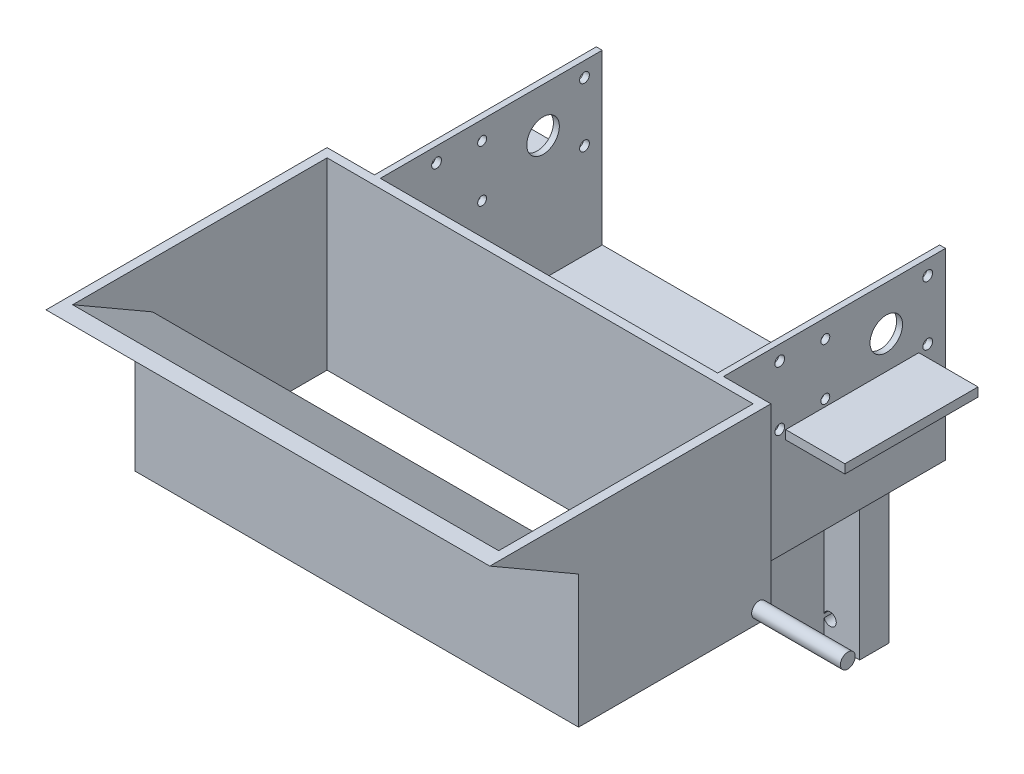
SolidWorks part; units mm, degrees
other "标注1"
sketch "草图12" plane through (40, 25, 80) normal (0.0849, 0.2202, 0.9717) x (0.9962, -0.0022, -0.0865)
ref_plane "前视基准面" through (0, 0, 0) normal (0, 0, 1) x (1, 0, 0)
ref_plane "上视基准面" through (0, 0, 0) normal (0, 1, 0) x (1, 0, 0)
ref_plane "右视基准面" through (0, 0, 0) normal (1, 0, 0) x (0, 0, -1)
sketch "草图1" plane through (0, 0, 0) normal (0, 0, 1) x (1, 0, 0)
  line L1 (-40, -25) -> (40, -25)
  line L2 (-40, -25) -> (-40, 25)
  line L3 (-40, 25) -> (40, 25)
  line L4 (40, -25) -> (40, 25)
  line L5 (-40, -25) -> (40, 25) construction
  line L6 (-40, 25) -> (40, -25) construction
  point P0 (0, 0)
  dimension "D1" = 80
  dimension "D2" = 50
extrude "凸台-拉伸1" add sketch "草图1" along normal blind 5
sketch "草图2" plane through (0, 0, 5) normal (0, 0, 1) x (1, 0, 0)
  line L0 (-1000, 0) -> (49000, 0) construction
  line L1 (0, -1000) -> (0, 49000) construction
  line L2 (-30, 20) -> (30, 20) construction
  line L3 (-30, 20) -> (-30, -20) construction
  line L4 (30, 20) -> (30, -20) construction
  line L5 (-30, -20) -> (30, -20) construction
  line L6 (0, 1000) -> (0, -49000) construction
  point P9 (0, 20)
  point P11 (30, 0)
  point P12 (-30, 0)
  point P14 (0, -20)
  dimension "D1" = 30
  dimension "D2" = 20
hole_wizard "M5 螺纹孔1" positions "草图3" profile "草图4" tap size "M5" standard "GB"
sketch "草图3" plane through (0, 0, 5) normal (0, 0, 1) x (1, 0, 0)
  point P0 (-30, 20)
  point P3 (-30, -20)
  point P6 (30, -20)
  point P9 (30, 20)
sketch "草图4" plane through (-30, 20, 5) normal (1, 0, 0) x (0, -1, 0)
  line L0 (0, 0) -> (0, 12.4)
  line L1 (0, 12.4) -> (2.1, 11.1382)
  line L2 (2.1, 11.1382) -> (2.1, 0)
  line L5 (2.1, 0) -> (0, 0)
  line L10 (0, 12.4) -> (-2.1, 11.1382) construction
  line L11 (0, -6.35) -> (0, 107.95) construction
  dimension "螺纹孔钻头直径" = 4.2
  dimension "螺纹孔钻头深度" = 12.4
  dimension "导头角度" = 118
cosmetic thread "孔螺蚊线1" parameters "D1"=10, "D2"=5
cosmetic thread "孔螺蚊线2" parameters "D1"=10, "D2"=5
cosmetic thread "孔螺蚊线3" parameters "D1"=10, "D2"=5
cosmetic thread "孔螺蚊线4" parameters "D1"=10, "D2"=5
sketch "草图5" plane through (40, 0, 0) normal (1, 0, 0) x (0, 0, -1)
  line L1 (0, -25) -> (-80, -25)
  line L2 (0, -25) -> (0, 25)
  line L3 (0, 25) -> (-80, 25)
  line L4 (-80, -25) -> (-80, 25)
  dimension "D1" = 50
  dimension "D2" = 80
extrude "凸台-拉伸2" add sketch "草图5" against normal blind 2 from offset 12 offset against normal yes
sketch "草图6" plane through (26, 0, 0) normal (-1, 0, 0) x (0, 0, 1)
  line L0 (11, 20) -> (61, 20) construction
  line L1 (61, 20) -> (61, 0) construction
  line L2 (61, 0) -> (11, 0) construction
  line L3 (11, 0) -> (11, 20) construction
  line L4 (5, 20) -> (5, -20) construction
  line L5 (5, 25) -> (80, 25) construction
  dimension "D1" = 50
  dimension "D2" = 20
  dimension "D3" = 6
  dimension "D4" = 5
hole_wizard "M4 螺纹孔1" positions "草图7" profile "草图8" tap size "M4" standard "GB"
sketch "草图7" plane through (26, 0, 0) normal (-1, 0, 0) x (0, 0, 1)
  point P0 (11, 20)
  point P3 (11, 0)
  point P6 (61, 20)
  point P9 (61, 0)
sketch "草图8" plane through (26, 20, 11) normal (0, 1, 0) x (0, 0, 1)
  line L0 (0, 0) -> (0, 10.1)
  line L1 (0, 10.1) -> (1.65, 9.1086)
  line L2 (1.65, 9.1086) -> (1.65, 0)
  line L5 (1.65, 0) -> (0, 0)
  line L10 (0, 10.1) -> (-1.65, 9.1086) construction
  line L11 (0, -6.35) -> (0, 107.95) construction
  dimension "螺纹孔钻头直径" = 3.3
  dimension "螺纹孔钻头深度" = 10.1
  dimension "导头角度" = 118
cosmetic thread "孔螺蚊线7" parameters "D1"=8, "D2"=4
cosmetic thread "孔螺蚊线8" parameters "D1"=8, "D2"=4
cosmetic thread "孔螺蚊线9" parameters "D1"=8, "D2"=4
cosmetic thread "孔螺蚊线10" parameters "D1"=8, "D2"=4
sketch "草图11" plane through (26, 0, 0) normal (-1, 0, 0) x (0, 0, 1)
  line L0 (25, 10) -> (62.4996, 10) construction
  line L2 (11, 0) -> (11, 20) construction
  line L5 (5, 25) -> (80, 25) construction
  line L9 (5, 25) -> (5, -25) construction
  circle A0 centre (25, 10) radius 5.5
  circle A1 centre (45.6, 18.75) radius 1.5
  circle A2 centre (45.6, 1.25) radius 1.5
  dimension "D1" = 11
  dimension "D2" = 3
  dimension "D3" = 17.5
  dimension "D4" = 20.6
  dimension "D5" = 15
  dimension "D6" = 20
extrude "切除-拉伸1" cut sketch "草图11" against normal through all
mirror "镜向1" about plane through (0, 0, 0) normal (1, 0, 0) of "凸台-拉伸2"
mirror "镜向2" about plane through (0, 0, 0) normal (1, 0, 0) of "M4 螺纹孔1", "切除-拉伸1"
cosmetic thread "孔螺蚊线11" parameters "D1"=8, "D2"=4
cosmetic thread "孔螺蚊线12" parameters "D1"=8, "D2"=4
cosmetic thread "孔螺蚊线13" parameters "D1"=8, "D2"=4
cosmetic thread "孔螺蚊线14" parameters "D1"=8, "D2"=4
sketch "草图13" plane through (0, -25, 0) normal (0, -1, 0) x (1, 0, 0)
  line L1 (-28, 80) -> (28, 80)
  line L2 (-28, 80) -> (-28, 5)
  line L3 (-28, 5) -> (28, 5)
  line L4 (28, 80) -> (28, 5)
  line L5 (-40, 5) -> (41.8748, 5)
  line L6 (-40, 5) -> (-40, -4.9337)
  line L7 (-40, -4.9337) -> (41.8748, -4.9337)
  line L8 (41.8748, 5) -> (41.8748, -4.9337)
  line M1 (-40, 0) -> (40, 0)
  line M2 (40, 0) -> (40, 5)
  line M3 (40, 5) -> (28, 5)
  line M4 (28, 5) -> (28, 80)
  line M5 (28, 80) -> (26, 80)
  line M6 (26, 80) -> (26, 5)
  line M7 (26, 5) -> (-26, 5)
  line M8 (-26, 5) -> (-26, 80)
  line M9 (-26, 80) -> (-28, 80)
  line M10 (-28, 80) -> (-28, 5)
  line M11 (-28, 5) -> (-40, 5)
  line M12 (-40, 5) -> (-40, 0)
extrude "切除-拉伸2" cut sketch "草图13" against normal through all both and the other way through all contours L3 M11 M12 M1 M2 M3 M7 | L8 L5 L6 L7 M2 M1 region at (0, -25, 2.5) region at (1.8445, -25, -2.3542)
sketch "草图14" plane through (0, 0, 5) normal (0, 0, -1) x (-1, 0, 0)
  line L1 (-28, 25) -> (28, 25)
  line L2 (-28, 25) -> (-28, -25)
  line L3 (-28, -25) -> (28, -25)
  line L4 (28, 25) -> (28, -25)
extrude "凸台-拉伸4" add sketch "草图13<3>" along normal blind 75 contours L1 M8 M7 M6 | L3 M10 M8 M9 | L3 M6 M4 M5 region at (-27, -25, 42.5) region at (0, -25, 42.5) region at (27, -25, 42.5)
sketch "草图13<3>" plane through (0, -25, 0) normal (0, -1, 0) x (1, 0, 0) same geometry as "草图13"
sketch "草图16" plane through (0, 0, 5) normal (0, 0, -1) x (-1, 0, 0)
  line L0 (0, -100) -> (0, -90.6573) construction
  line L2 (-28, -100) -> (28, -100) construction
  line L3 (-40, -100) -> (40, -100)
  line L4 (-40, -100) -> (-40, -46)
  line L5 (-40, -46) -> (40, -46)
  line L6 (40, -100) -> (40, -46)
  line L7 (30, -73) -> (18.1128, -73) construction
  circle A0 centre (-30, -93) radius 2.1
  circle A1 centre (30, -93) radius 2.1
  circle A2 centre (-30, -53) radius 2.1
  circle A3 centre (30, -53) radius 2.1
  point P15 (0, -46)
  dimension "D1" = 4.2
  dimension "D3" = 4.2
  dimension "D2" = 30
  dimension "D4" = 40
  dimension "D5" = 40
  dimension "D6" = 7
  dimension "D7" = 20
  dimension "D8" = 27
  dimension "D9" = 60
extrude "凸台-拉伸5" add sketch "草图16" against normal blind 10
sketch "草图17" plane through (0, 0, 80) normal (0, 0, 1) x (1, 0, 0)
  line L0 (-26, -49) -> (-26, -100)
  line L1 (26, -49) -> (26, -100)
  line L2 (-26, -49) -> (26, -49)
  line L3 (0, -100) -> (0, -92.4239) construction
  line L8 (28, -100) -> (28, 25)
  line L9 (28, 25) -> (26, 25)
  line L10 (26, 25) -> (26, -25)
  line L11 (26, -25) -> (-26, -25)
  line L12 (-26, -25) -> (-26, 25)
  line L13 (-26, 25) -> (-28, 25)
  line L14 (-28, 25) -> (-28, -100)
  line L15 (-28, -100) -> (28, -100)
  line L23 (-26, -100) -> (26, -100)
  dimension "D2" = 51
  dimension "D3" = 52
  dimension "D4" = 26
  dimension "D1" = 0
extrude "切除-拉伸4" cut sketch "草图17" against normal up to surface (65 mm away) up to face at (32.025, -73, 15)
sketch "草图18" plane through (0, 0, 80) normal (0, 0, 1) x (1, 0, 0)
  line L0 (0, -10.6953) -> (0, -25) construction
  line L1 (-50, 25) -> (50, 25)
  line L2 (-50, 25) -> (-50, -25)
  line L3 (-50, -25) -> (50, -25)
  line L4 (50, 25) -> (50, -25)
  line L5 (-26, -49) -> (26, -49) construction
  line L6 (-48, 25) -> (-48, -20)
  line L7 (48, 25) -> (48, -20)
  line L9 (-48, -20) -> (48, -20)
  point P5 (0, 25)
  line M11 (28, -100) -> (28, 25)
  line M13 (26, 25) -> (26, -25)
  line M14 (26, -25) -> (-26, -25)
  line M15 (-26, -25) -> (-26, 25)
  line M17 (-28, 25) -> (-28, -100)
  dimension "D1" = 50
  dimension "D2" = 50
  dimension "D3" = 74
  dimension "D4" = 2
  dimension "D5" = 2
  dimension "D6" = 5
extrude "凸台-拉伸6" add sketch "草图18" against normal up to surface (75 mm away) contours L9 L6 L1 L2 L3 M17 | L0 L9 L3 M15 | L9 L3 M17 M15 | L9 L0 M14 M13 | L9 L3 M13 M11 | L9 L3 L4 L1 L7 M11 region at (13, -22.5, 80) region at (-13, -22.5, 80) region at (-27, -22.5, 80) region at (27, -22.5, 80) region at (-28.5463, -22.5, 80) region at (38, -20.5463, 80) up to face at (30.05, -53, 5)
sketch "草图19" plane through (-50, 0, 0) normal (-1, 0, 0) x (0, 0, 1)
  line L4 (80, 25) -> (5, 25)
  line L5 (5, 25) -> (5, -25)
  line L6 (5, -25) -> (80, -25)
  line L7 (80, -25) -> (80, 25)
  line L8 (80, 25) -> (5, 25)
  line L9 (5, 25) -> (5, -25)
  line L10 (5, -25) -> (80, -25)
  line L11 (80, -25) -> (80, 25)
  circle A0 centre (45.6, 1.25) radius 1.5 construction
  circle A1 centre (45.6, 18.75) radius 1.5 construction
  circle A2 centre (25, 10) radius 5.5 construction
  circle A3 centre (45.6, 1.25) radius 1.5
  circle A4 centre (45.6, 18.75) radius 1.5
  circle A5 centre (25, 10) radius 5.5
  dimension "D1" = 0
extrude "切除-拉伸5" cut sketch "草图19" against normal through all both and the other way through all contours A5 | A4 | A3 region at (-50, 1.25, 45.6) region at (-50, 18.75, 45.6) region at (-50, 10, 25)
sketch "草图20" plane through (-50, 0, 0) normal (-1, 0, 0) x (0, 0, 1)
  line L0 (61, 20) -> (61, 0) construction
  line L1 (61, 0) -> (11, 0) construction
  line L2 (11, 0) -> (11, 20) construction
  line L3 (11, 20) -> (61, 20) construction
  line L4 (61, 20) -> (61, 0) construction
  line L5 (61, 0) -> (11, 0) construction
  line L6 (11, 0) -> (11, 20) construction
  line L7 (11, 20) -> (61, 20) construction
ref_plane "基准面1" through (-50, 0, 0) normal (-1, 0, 0) x (0, 0, 1)
ref_plane "基准面2" through (-11, 0, 0) normal (-1, 0, 0) x (0, 0, 1)
mirror "镜向3" about plane through (-11, 0, 0) normal (-1, 0, 0) of "M4 螺纹孔1"
cosmetic thread "孔螺蚊线15" parameters "D1"=8, "D2"=4
cosmetic thread "孔螺蚊线16" parameters "D1"=8, "D2"=4
cosmetic thread "孔螺蚊线17" parameters "D1"=8, "D2"=4
cosmetic thread "孔螺蚊线18" parameters "D1"=8, "D2"=4
ref_plane "基准面3" through (50, 0, 0) normal (1, 0, 0) x (0, 0, -1)
ref_plane "基准面4" through (38, 0, 0) normal (1, 0, 0) x (0, 0, -1)
mirror "镜向4" about plane through (38, 0, 0) normal (1, 0, 0) of "M4 螺纹孔1"
cosmetic thread "孔螺蚊线19" parameters "D1"=8, "D2"=4
cosmetic thread "孔螺蚊线20" parameters "D1"=8, "D2"=4
cosmetic thread "孔螺蚊线21" parameters "D1"=8, "D2"=4
cosmetic thread "孔螺蚊线22" parameters "D1"=8, "D2"=4
sketch "草图21" plane through (0, 0, 80) normal (0, 0, 1) x (1, 0, 0)
  line L0 (-31.7586, 26.7655) -> (-31.7586, -20)
  line L1 (-48, -20) -> (-28, -20) construction
  line L2 (-31.7586, -20) -> (32.4376, -20)
  line L3 (28, -20) -> (48, -20) construction
  line L4 (32.4376, -20) -> (32.4376, 28.4059)
  line L5 (32.4376, 28.4059) -> (-31.7586, 26.7655)
extrude "切除-拉伸6" cut sketch "草图21" against normal through all both and the other way through all
sketch "草图22" plane through (0, 0, 80) normal (0, 0, 1) x (1, 0, 0)
  line L0 (-50, -25) -> (-28, -25) construction
  line L1 (-55, 25) -> (55, 25)
  line L2 (-55, 25) -> (-55, -25)
  line L3 (-55, -25) -> (55, -25)
  line L4 (55, 25) -> (55, -25)
  line L5 (-50, 25) -> (-48, 25) construction
  line L6 (0, -20) -> (0, 1.8911) construction
  line L8 (-53, 25) -> (-53, -20)
  line L9 (53, 25) -> (53, -20)
  line L10 (-53, -20) -> (53, -20)
  point P9 (0, 25)
  line M9 (48, -20) -> (-48, -20)
  line M12 (-50, 25) -> (-50, -25)
  line M13 (-50, -25) -> (-28, -25)
  line M21 (28, -25) -> (50, -25)
  line M22 (50, -25) -> (50, 25)
  dimension "D1" = 55
  dimension "D2" = 2
  dimension "D3" = 2
extrude "凸台-拉伸7" add sketch "草图22" against normal up to surface (75 mm away) contours L3 L6 L10 M12 M13 | L10 L8 L1 L2 L3 M12 | L6 L3 L10 M21 M22 M9 | L10 L3 L4 L1 L9 M22 region at (-53.6739, -2.9348, 80) region at (0, -22.5, 80) region at (53.6739, -2.9348, 80) up to face at (0, -26.5, 5)
ref_plane "基准面6" through (-51.5, 0, 0) normal (1, 0, 0) x (0, 0, -1)
mirror "镜向8" about plane through (-51.5, 0, 0) normal (1, 0, 0) of "切除-拉伸5"
sketch "草图23" plane through (-55, 0, 0) normal (-1, 0, 0) x (0, 0, 1)
  line L0 (61, 20) -> (61, 0) construction
  line L1 (11, 20) -> (61, 20) construction
  line L2 (11, 0) -> (11, 20) construction
  line L3 (61, 0) -> (11, 0) construction
  line L4 (61, 20) -> (61, 0) construction
  line L5 (11, 20) -> (61, 20) construction
  line L6 (11, 0) -> (11, 20) construction
  line L7 (61, 0) -> (11, 0) construction
ref_plane "基准面7" through (2.5, 0, 0) normal (-1, 0, 0) x (0, 0, 1)
mirror "镜向16" about plane through (2.5, 0, 0) normal (-1, 0, 0) of "镜向3"
cosmetic thread "孔螺蚊线23" parameters "D1"=8, "D2"=4
cosmetic thread "孔螺蚊线24" parameters "D1"=8, "D2"=4
cosmetic thread "孔螺蚊线25" parameters "D1"=8, "D2"=4
cosmetic thread "孔螺蚊线26" parameters "D1"=8, "D2"=4
mirror "镜向18" about plane through (0, 0, 0) normal (1, 0, 0) of "镜向16"
cosmetic thread "孔螺蚊线27" parameters "D1"=8, "D2"=4
cosmetic thread "孔螺蚊线28" parameters "D1"=8, "D2"=4
cosmetic thread "孔螺蚊线29" parameters "D1"=8, "D2"=4
cosmetic thread "孔螺蚊线30" parameters "D1"=8, "D2"=4
sketch "草图24" plane through (0, 0, 5) normal (0, 0, -1) x (-1, 0, 0)
  line L0 (50, -20) -> (53, -20) construction
  line L1 (-51.4758, 28.456) -> (51.5, 28.456)
  line L2 (-51.4758, 28.456) -> (-51.4758, -20)
  line L3 (-51.4758, -20) -> (51.5, -20)
  line L4 (51.5, 28.456) -> (51.5, -20)
extrude "切除-拉伸7" cut sketch "草图24" against normal through all both and the other way through all
sketch "草图25" plane through (0, 0, 5) normal (0, 0, -1) x (-1, 0, 0)
  line L0 (0, -20) -> (0, -32.9926) construction
  line L6 (-55, 25) -> (-55, -25) construction
  line L7 (-53, -25) -> (-53, -32)
  line L8 (-53, -32) -> (53, -32)
  line L9 (-55, -25) -> (-55, -37)
  line L10 (-55, -37) -> (55, -37)
  line L11 (53, -25) -> (53, -32)
  line L12 (55, -25) -> (55, -37)
  line L13 (55, -25) -> (28, -25) construction
  line L14 (-55, -25) -> (-53, -25)
  line L15 (53, -25) -> (55, -25)
  point P13 (0, -37)
  point P16 (0, -32)
  dimension "D1" = 5
  dimension "D2" = 12
  dimension "D3" = 2
extrude "凸台-拉伸8" add sketch "草图25" against normal up to surface (75 mm away) up to face at (0, -33.625, 80)
sketch "草图26" plane through (0, 0, 5) normal (0, 0, -1) x (-1, 0, 0)
  line L0 (-53, -20) -> (-53, -32)
  line L1 (-53, -32) -> (53, -32)
  line L2 (53, -32) -> (53, -15.707)
  line L3 (53, 25) -> (53, -20) construction
  line L4 (53, -15.707) -> (-53, -15.707)
  line L5 (-53, 25) -> (-53, -20) construction
  line L6 (-53, -15.707) -> (-53, -20)
extrude "切除-拉伸8" cut sketch "草图26" against normal through all both and the other way through all
sketch "草图27" plane through (0, 0, 5) normal (0, 0, -1) x (-1, 0, 0)
  line L0 (0, -32) -> (0, -12.5887) construction
  line L2 (-59, 25) -> (-59, -37)
  line L3 (-59, -37) -> (59, -37)
  line L4 (59, 25) -> (59, -37)
  line L5 (55, 25) -> (55, -37) construction
  line L6 (-55, 25) -> (-55, -37) construction
  line L7 (-55, -37) -> (-28, -37) construction
  line L8 (59, 25) -> (57, 25)
  line L9 (57, 25) -> (57, -32)
  line L10 (57, -32) -> (-57, -32)
  line L11 (-57, -32) -> (-57, 25)
  line L12 (-57, 25) -> (-59, 25)
  line L13 (53, -32) -> (-53, -32) construction
  dimension "D1" = 4
  dimension "D2" = 4
  dimension "D3" = 2
  dimension "D4" = 2
  dimension "D5" = 62
extrude "凸台-拉伸9" add sketch "草图27" against normal up to surface (75 mm away) up to face at (0, -38.125, 80)
ref_plane "基准面8" through (56, 0, 0) normal (1, 0, 0) x (0, 0, -1)
mirror "镜向20" about plane through (56, 0, 0) normal (1, 0, 0) of "镜向8", "镜向16"
cosmetic thread "孔螺蚊线31" parameters "D1"=8, "D2"=4
cosmetic thread "孔螺蚊线32" parameters "D1"=8, "D2"=4
cosmetic thread "孔螺蚊线33" parameters "D1"=8, "D2"=4
cosmetic thread "孔螺蚊线34" parameters "D1"=8, "D2"=4
mirror "镜向22" about plane through (0, 0, 0) normal (1, 0, 0) of "镜向20"
cosmetic thread "孔螺蚊线35" parameters "D1"=8, "D2"=4
cosmetic thread "孔螺蚊线36" parameters "D1"=8, "D2"=4
cosmetic thread "孔螺蚊线37" parameters "D1"=8, "D2"=4
cosmetic thread "孔螺蚊线38" parameters "D1"=8, "D2"=4
sketch "草图28" plane through (0, 0, 5) normal (0, 0, -1) x (-1, 0, 0)
  line L0 (-56, 31.35) -> (-56, -31.35) construction
  line L1 (-56, 27.6586) -> (56, 27.6586)
  line L2 (-56, 27.6586) -> (-56, -32)
  line L3 (-56, -32) -> (56, -32)
  line L4 (56, 27.6586) -> (56, -32)
  line L5 (57, -32) -> (55, -32) construction
extrude "切除-拉伸9" cut sketch "草图28" against normal blind 100
sketch "草图29" plane through (0, 0, 80) normal (0, 0, 1) x (1, 0, 0)
  line L0 (0, -32) -> (0, -19.2163) construction
  line L2 (-75, 25) -> (75, 25)
  line L3 (28, 25) -> (-28, 25) construction
  line L4 (-75, 25) -> (-75, -37.1567)
  line L5 (-75, -37.1567) -> (75, -37.1567)
  line L6 (75, 25) -> (75, -37.1567)
  point P12 (0, 25)
  point P13 (0, -37.1567)
  dimension "D1" = 75
  dimension "D2" = 62.1567
extrude "凸台-拉伸10" add sketch "草图29" along normal blind 95
sketch "草图30" plane through (-75, 0, 0) normal (-1, 0, 0) x (0, 0, 1)
  line L0 (175, 25) -> (145, 7.6795)
  line L1 (145, 7.6795) -> (145, -37.1567)
  line L2 (175, -37.1567) -> (80, -37.1567) construction
  line L3 (175, 25) -> (175, -37.1567) construction
  dimension "D1" = 30
  dimension "D2" = 60
extrude "切除-拉伸10" cut sketch "草图30" against normal through all and the other way through all
sketch "草图31" plane through (-75, 0, 0) normal (-1, 0, 0) x (0, 0, 1)
  line L0 (83, 29.8275) -> (177.3615, 29.8275)
  line L1 (177.3615, 29.8275) -> (142, 9.4115)
  line L2 (142, 9.4115) -> (142, -50.3087)
  line L3 (142, -50.3087) -> (83, -50.3087)
  line L4 (83, -50.3087) -> (83, 29.8275)
  line L6 (80, 25) -> (80, -37.1567) construction
  line L7 (175, 25) -> (145, 7.6795) construction
  line L8 (145, 7.6795) -> (145, -37.1567) construction
  dimension "D2" = 3
  dimension "D3" = 3
  dimension "D4" = 3
extrude "切除-拉伸11" cut sketch "草图31" against normal offset from surface (144 mm away) 3 from offset 3 up to face at (75, -3.3268, 125) offset against normal yes
sketch "草图32" plane through (28, 0, 0) normal (1, 0, 0) x (0, 0, -1)
  line L0 (-80, -37.1567) -> (-15, -100)
  line L1 (-15, -100) -> (-94.5487, -113.2548)
  line L2 (-94.5487, -113.2548) -> (-80, -37.1567)
extrude "切除-拉伸12" cut sketch "草图32" along normal through all both and the other way through all
sketch "草图34" plane through (59, 0, 0) normal (1, 0, 0) x (0, 0, -1)
  line L0 (-80, 25) -> (-80, -37) construction
  line L1 (-5, 25) -> (-5, -25) construction
  line L3 (-14, -1.05) -> (-59, -1.05)
  line L4 (-80, 25) -> (-5, 25) construction
  line L5 (-59, -1.05) -> (-59, -4.05)
  line L6 (-59, -4.05) -> (-14, -4.05)
  line L7 (-14, -4.05) -> (-14, -1.05)
  dimension "D1" = 3
  dimension "D2" = 21
  dimension "D3" = 26.05
  dimension "D4" = 9
extrude "凸台-拉伸11" add sketch "草图34" along normal blind 20
extrude "凸台-拉伸12" add sketch "草图34<3>" against normal blind 20 from surface starting at face at (-59, 0, 59.35)
sketch "草图34<3>" plane through (59, 0, 0) normal (1, 0, 0) x (0, 0, -1) same geometry as "草图34"
sketch "草图35" plane through (75, 0, 0) normal (1, 0, 0) x (0, 0, -1)
  line L0 (-80, 25) -> (-80, -37) construction
  line L3 (-145, -37.1567) -> (-80, -37.1567) construction
  circle A0 centre (-84, -33.1567) radius 2.5
  point P6 (-83.421, -37.1567)
  point P7 (-107.2385, -37.1567)
  dimension "D1" = 5
  dimension "D2" = 4
  dimension "D3" = 4
extrude "凸台-拉伸13" add sketch "草图35" along normal blind 30
sketch "草图36" plane through (-75, 0, 0) normal (-1, 0, 0) x (0, 0, 1)
  circle A1 centre (84, -33.1567) radius 2.5
  circle A2 centre (84, -33.1567) radius 2.5
  dimension "D1" = 0
extrude "凸台-拉伸14" add sketch "草图36" along normal blind 30
